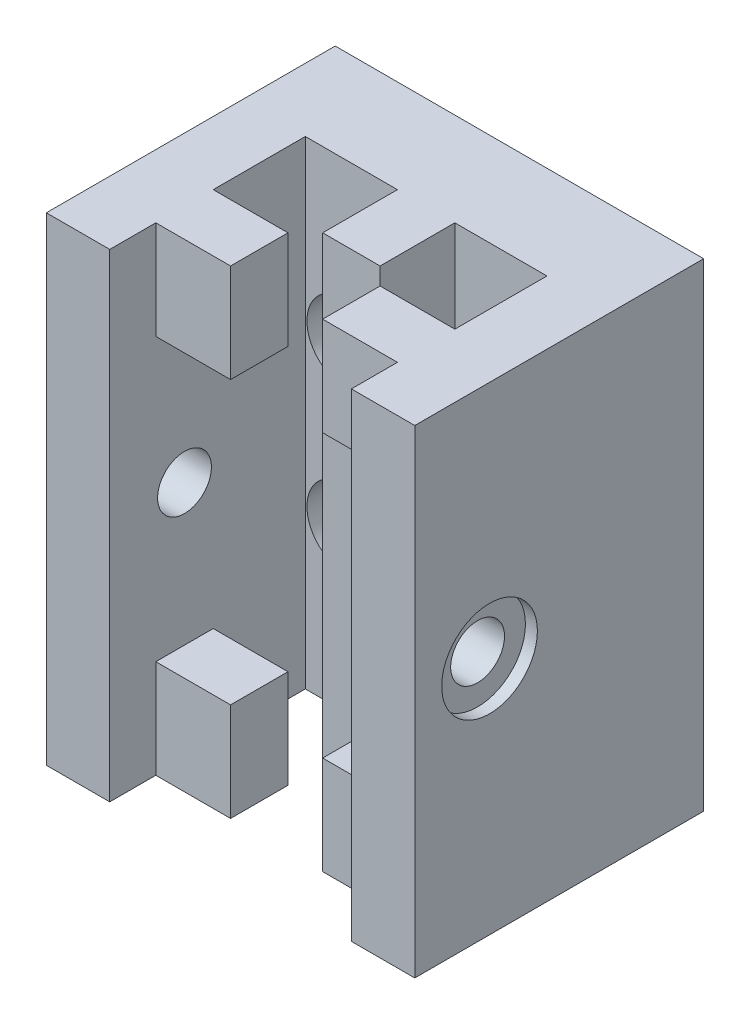
SolidWorks part; units mm, degrees
ref_plane "Plan de face" through (0, 0, 0) normal (0, 0, 1) x (1, 0, 0)
ref_plane "Plan de dessus" through (0, 0, 0) normal (0, 1, 0) x (1, 0, 0)
ref_plane "Plan de droite" through (0, 0, 0) normal (1, 0, 0) x (0, 0, -1)
sketch "Base" plane through (0, 0, 0) normal (0, 1, 0) x (1, 0, 0)
  line L0 (-3.85, -2.4) -> (-3.85, 2.4)
  line L1 (-3.85, 2.4) -> (-10.1, 2.4)
  line L2 (-10.1, 2.4) -> (-10.1, 10.1)
  line L3 (-10.1, 10.1) -> (-2.4, 10.1)
  line L4 (-2.4, 10.1) -> (-2.4, 3.85)
  line L5 (-2.4, 3.85) -> (2.4, 3.85)
  line L6 (0, -55) -> (0, 55) construction
  line L7 (2.4, 10.1) -> (2.4, 3.85)
  line L8 (10.1, 10.1) -> (2.4, 10.1)
  line L9 (10.1, 2.4) -> (10.1, 10.1)
  line L10 (3.85, 2.4) -> (10.1, 2.4)
  line L11 (3.85, -2.4) -> (3.85, 2.4)
  line L12 (-55, 0) -> (55, 0) construction
  line L13 (3.85, -2.4) -> (10.1, -2.4)
  line L14 (10.1, -2.4) -> (10.1, -6.25)
  line L20 (-10.1, -2.4) -> (-10.1, -6.25)
  line L21 (-3.85, -2.4) -> (-10.1, -2.4)
  line L23 (-15.4, 15.4) -> (15.4, 15.4)
  line L24 (-15.4, 15.4) -> (-15.4, -6.25)
  line L26 (15.4, 15.4) -> (15.4, -6.25)
  line L27 (-15.4, 15.4) -> (0, 0) construction
  line L28 (0, 0) -> (15.4, 15.4) construction
  line L29 (-10.1, -6.25) -> (-15.4, -6.25)
  line L30 (10.1, -6.25) -> (15.4, -6.25)
  line L31 (10.1, -10.1) -> (15.4, -15.4) construction
  point P2 (-3.85, 0)
  point P3 (0, 3.85)
  point P27 (0, 0)
  dimension "D1" = 4.8
  dimension "D2" = 4.8
  dimension "D3" = 6.25
  dimension "D4" = 7.7
  dimension "D5" = 30.8
extrude "Boss.-Extru.1" add sketch "Base" along normal mid plane 40
hole_wizard "Chambrage pour vis à six pans creux M41" positions "Esquisse4" profile "Esquisse5" counterbore size "M4" standard "ISO" end condition up to next
sketch "Esquisse4" plane through (15.4, 0, 0) normal (1, 0, 0) x (0, 0, -1)
  point P0 (0, 0)
sketch "Esquisse5" plane through (15.4, 0, 0) normal (0, 1, 0) x (0, 0, -1)
  line L0 (0, 0) -> (0, 11.55)
  line L1 (0, 11.55) -> (2.25, 11.55)
  line L3 (2.25, 11.55) -> (2.25, 1)
  line L4 (2.25, 1) -> (4, 1)
  line L5 (4, 1) -> (4, 0)
  line L7 (4, 0) -> (0, 0)
  line L11 (0, -6.35) -> (0, 107.95) construction
  dimension "Diamètre du perçage jusqu'au prochain" = 4.5
  dimension "Profondeur du perçage jusqu'au prochain" = 11.55
  dimension "Diamètre du chambrage" = 8
  dimension "Profondeur du chambrage" = 1
mirror "Symétrie1" about plane through (0, 0, 0) normal (1, 0, 0) of "Chambrage pour vis à six pans creux M41"
sketch "Esquisse6" plane through (0, 0, 0) normal (0, 0, 1) x (1, 0, 0)
  line L0 (10.1, 20) -> (10.1, -20) construction
  line L1 (-10.1, 11.7753) -> (10.1, 11.7753)
  line L2 (-10.1, 11.7753) -> (-10.1, -11.7753)
  line L3 (-10.1, -11.7753) -> (10.1, -11.7753)
  line L4 (10.1, 11.7753) -> (10.1, -11.7753)
  line L5 (-10.1, 11.7753) -> (10.1, -11.7753) construction
  line L6 (-10.1, -11.7753) -> (10.1, 11.7753) construction
  point P0 (0, 0)
extrude "Enlèv. mat.-Extru.1" cut sketch "Esquisse6" against normal mid plane 6
sketch "Esquisse7" plane through (0, 0, -10.1) normal (0, 0, 1) x (1, 0, 0)
  line L1 (-6.7175, 6.7175) -> (6.7175, 6.7175) construction
  line L2 (-6.7175, 6.7175) -> (-6.7175, -6.7175) construction
  line L3 (-6.7175, -6.7175) -> (6.7175, -6.7175) construction
  line L4 (6.7175, 6.7175) -> (6.7175, -6.7175) construction
  line L5 (-6.7175, 6.7175) -> (6.7175, -6.7175) construction
  line L6 (-6.7175, -6.7175) -> (6.7175, 6.7175) construction
  circle A0 centre (0, 0) radius 9.5 construction
  dimension "D1" = 19
sketch "Esquisse14" plane through (0, -20, 0) normal (0, -1, 0) x (1, 0, 0)
  line L0 (15.4, 6.25) -> (15.4, -15.4) construction
  line L1 (-15.4, -15.4) -> (15.4, -15.4)
  line L2 (-15.4, -15.4) -> (-15.4, -17.9)
  line L3 (-15.4, -17.9) -> (15.4, -17.9)
  line L4 (15.4, -15.4) -> (15.4, -17.9)
  dimension "D1" = 2.5
extrude "Boss.-Extru.3" add sketch "Esquisse14" against normal up to vertex (40 mm away) up to point (-15.4, 20, -15.4)
hole_wizard "Chambrage pour vis à six pans creux M31" positions "Esquisse10" profile "Esquisse12" counterbore size "M3" standard "ISO" end condition up to next
sketch "Esquisse10" plane through (0, 0, -10.1) normal (0, 0, 1) x (1, 0, 0)
  point P0 (-6.7175, 6.7175)
  point P3 (-6.7175, -6.7175)
  point P7 (6.7175, 6.7175)
  point P10 (6.7175, -6.7175)
sketch "Esquisse12" plane through (-6.7175, 6.7175, -10.1) normal (1, 0, 0) x (0, -1, 0)
  line L0 (0, 0) -> (0, 7.8)
  line L1 (0, 7.8) -> (1.7, 7.8)
  line L3 (1.7, 7.8) -> (1.7, 3.4)
  line L4 (1.7, 3.4) -> (3.25, 3.4)
  line L5 (3.25, 3.4) -> (3.25, 0)
  line L7 (3.25, 0) -> (0, 0)
  line L11 (0, -6.35) -> (0, 107.95) construction
  dimension "Diamètre du perçage jusqu'au prochain" = 3.4
  dimension "Profondeur du perçage jusqu'au prochain" = 7.8
  dimension "Diamètre du chambrage" = 6.5
  dimension "Profondeur du chambrage" = 3.4
